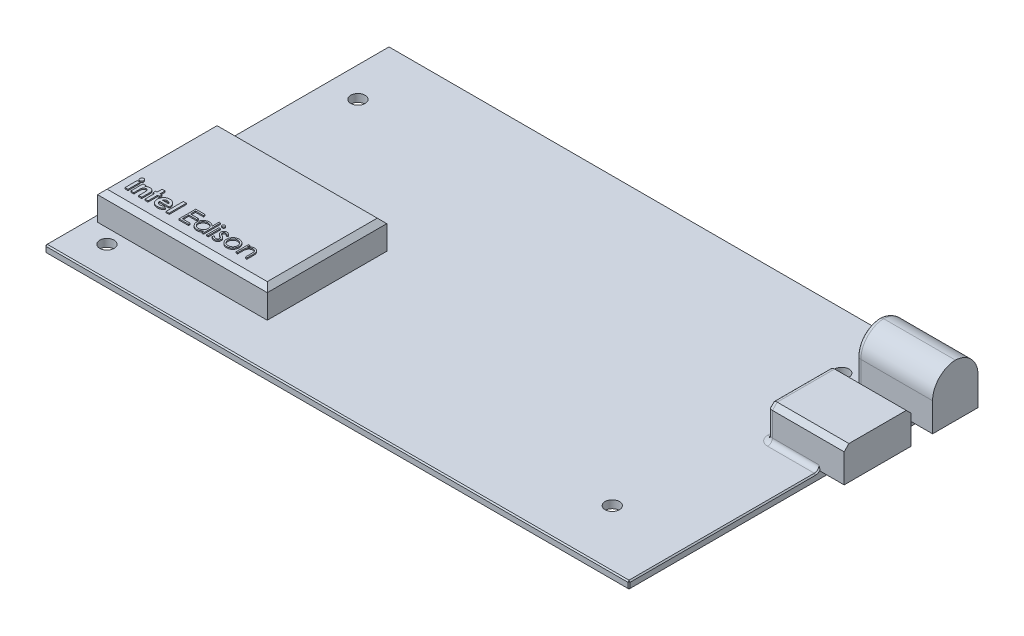
SolidWorks part; units mm, degrees
ref_plane "Front Plane" through (0, 0, 0) normal (0, 0, 1) x (1, 0, 0)
ref_plane "Top Plane" through (0, 0, 0) normal (0, 1, 0) x (1, 0, 0)
ref_plane "Right Plane" through (0, 0, 0) normal (1, 0, 0) x (0, 0, -1)
sketch "Sketch1" plane through (0, 0, 0) normal (0, 1, 0) x (1, 0, 0)
  line L1 (0, 0) -> (122.2, 0)
  line L2 (0, 0) -> (0, 72)
  line L3 (0, 72) -> (122.2, 72)
  line L4 (122.2, 0) -> (122.2, 72)
  dimension "D1" = 122.2
  dimension "D2" = 72
extrude "Boss-Extrude1" add sketch "Sketch1" along normal blind 1.62
sketch "Sketch2" plane through (0, 1.62, 0) normal (0, 1, 0) x (1, 0, 0)
  line L0 (122.2, 0) -> (122.2, 72) construction
  line L1 (122.2, 68) -> (111.2, 68)
  line L2 (122.2, 68) -> (122.2, 40)
  line L3 (122.2, 40) -> (111.2, 40)
  line L4 (111.2, 68) -> (111.2, 40)
  dimension "D1" = 4
  dimension "D2" = 28
  dimension "D3" = 11
extrude "Boss-Extrude2" add sketch "Sketch2" along normal blind 11
sketch "Sketch3" plane through (0, 12.62, 0) normal (0, 1, 0) x (1, 0, 0)
  line L0 (111.2, 68) -> (111.2, 40) construction
  line L1 (122.2, 40) -> (111.2, 40)
  line L2 (122.2, 40) -> (122.2, 54)
  line L3 (122.2, 54) -> (111.2, 54)
  line L4 (111.2, 40) -> (111.2, 54)
  line L5 (122.2, 40) -> (122.2, 68) construction
  line L6 (111.2, 54) -> (122.2, 54)
  line L7 (111.2, 54) -> (111.2, 58.5)
  line L8 (111.2, 58.5) -> (122.2, 58.5)
  line L9 (122.2, 54) -> (122.2, 58.5)
  line M1 (122.2, 40) -> (122.2, 68)
  line M3 (111.2, 68) -> (111.2, 40)
  line M4 (111.2, 40) -> (122.2, 40)
  dimension "D1" = 14
  dimension "D2" = 4.5
extrude "Cut-Extrude1" cut sketch "Sketch3" against normal blind 4 contours L3 M1 M3 M4 region at (116.7, 12.62, -47)
extrude "Cut-Extrude2" cut sketch "Sketch3<5>" against normal blind 11 contours L8 L3 M3 M1 region at (116.7, 12.62, -56.25)
sketch "Sketch3<5>" plane through (0, 12.62, 0) normal (0, 1, 0) x (1, 0, 0) same geometry as "Sketch3"
sketch "Sketch5" plane through (122.2, 0, 0) normal (1, 0, 0) x (0, 0, -1)
  line L0 (40, 1.62) -> (54, 1.62)
  line L1 (54, 1.62) -> (54, 8.62)
  line L2 (54, 8.62) -> (40, 8.62)
  line L3 (40, 8.62) -> (40, 1.62)
  line L4 (58.5, 1.62) -> (68, 1.62)
  line L5 (68, 1.62) -> (68, 12.62)
  line L6 (68, 12.62) -> (58.5, 12.62)
  line L7 (58.5, 12.62) -> (58.5, 1.62)
extrude "Boss-Extrude3" add sketch "Sketch5" along normal blind 5
fillet "Fillet1" radius 5 2 edges at (119.2, 12.62, -68) (119.2, 12.62, -58.5)
chamfer "Chamfer1" distance 1 angle 45 2 edges at (119.2, 8.62, -54) (119.2, 8.62, -40)
fillet "Fillet2" radius 1 15 edges at (116.7, 1.62, -58.5) (116.7, 1.62, -54) (111.2, 4.62, -58.5) (111.2, 1.62, -63.25) (111.2, 4.62, -68) (111.2, 11.066, -66.6228) (111.2, 11.066, -59.8772) (111.2, 8.12, -40.5) (111.2, 4.62, -40) (111.2, 1.62, -47) (111.2, 4.62, -54) (111.2, 8.12, -53.5) (111.2, 8.62, -47)
sketch "Sketch4" plane through (0, 1.62, 0) normal (0, 1, 0) x (1, 0, 0)
  line L0 (6.5, 72) -> (6.5, 0) construction
  line L1 (122.2, 72) -> (0, 72) construction
  line L2 (0, 0) -> (122.2, 0) construction
  line L3 (0, 59) -> (31.5387, 59) construction
  line L4 (0, 72) -> (0, 0) construction
  line L5 (0, 6.5) -> (31.5387, 6.5) construction
  line L6 (106.7, 72) -> (106.7, 0) construction
  line L7 (122.2, 60) -> (88.3421, 60) construction
  line L8 (122.2, 12) -> (89.0191, 12) construction
  line L9 (122.2, 0) -> (122.2, 39) construction
  circle A0 centre (6.5, 59) radius 1.5
  circle A1 centre (6.5, 6.5) radius 1.5
  circle A2 centre (106.7, 12) radius 1.5
  circle A3 centre (106.7, 60) radius 1.5
  point P23 (6.5, 59)
  point P24 (6.5, 6.5)
  point P26 (106.7, 12)
  point P27 (106.7, 60)
  dimension "D7" = 3
  dimension "D8" = 3
  dimension "D9" = 3
  dimension "D10" = 3
  dimension "D1" = 6.5
  dimension "D2" = 13
  dimension "D3" = 6.5
  dimension "D4" = 15.5
  dimension "D5" = 12
  dimension "D6" = 12
extrude "Cut-Extrude3" cut sketch "Sketch4" against normal through all
sketch "Sketch6" plane through (0, 1.62, 0) normal (0, 1, 0) x (1, 0, 0)
  line L0 (0, 72) -> (0, 0) construction
  line L1 (1.5349, 9.5) -> (37.0349, 9.5)
  line L2 (1.5349, 9.5) -> (1.5349, 34.5)
  line L3 (1.5349, 34.5) -> (37.0349, 34.5)
  line L4 (37.0349, 9.5) -> (37.0349, 34.5)
  line L5 (0, 0) -> (122.2, 0) construction
  dimension "D1" = 1.5349
  dimension "D2" = 9.5
  dimension "D3" = 25
  dimension "D4" = 35.5
extrude "Boss-Extrude4" add sketch "Sketch6" along normal blind 6
chamfer "Chamfer2" distance 1 angle 45 4 edges at (19.2849, 7.62, -34.5) (37.0349, 7.62, -22) (19.2849, 7.62, -9.5) (1.5349, 7.62, -22)
sketch "Sketch7" plane through (0, 7.62, 0) normal (0, 1, 0) x (1, 0, 0)
  text T0 "<b>intel </b>Edison"
extrude "Boss-Extrude5" add sketch "Sketch7" along normal blind 0.25
chamfer "Chamfer3" distance 0.25 angle 45 18 edges at (122.2, 1.9129, -54.2929) (122.2, 1.9129, -58.2071) (122.2, 1.62, -56.25) (122.2, 1.9129, -39.7071) (122.2, 1.9129, -68.2929) (122.2, 0.81, 0) (122.2, 0, -36) (122.2, 0.81, -72) (61.1, 0, -72) (61.1, 1.62, -72) (0, 0.81, -72) (0, 0, -36) (0, 1.62, -36) (61.1, 0, 0) (0, 0.81, 0) (61.1, 1.62, 0)
